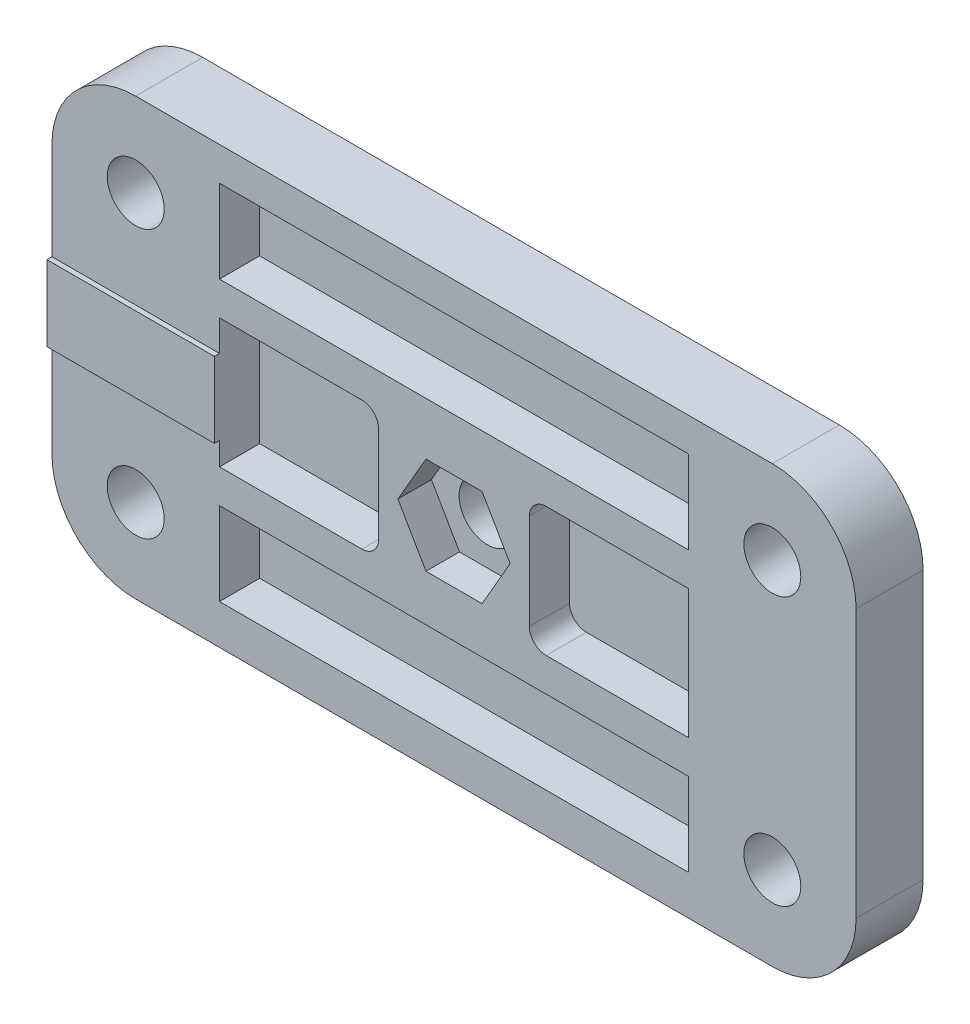
SolidWorks part; units mm, degrees
ref_plane "Front Plane" through (0, 0, 0) normal (0, 0, 1) x (1, 0, 0)
ref_plane "Top Plane" through (0, 0, 0) normal (0, 1, 0) x (1, 0, 0)
ref_plane "Right Plane" through (0, 0, 0) normal (1, 0, 0) x (0, 0, -1)
sketch "Sketch1" plane through (0, 0, 0) normal (0, 0, 1) x (1, 0, 0)
  line L0 (-19, 0) -> (19, 0) construction
  line L1 (-19, -8) -> (19, -8) construction
  line L2 (-19, -8) -> (-19, 8) construction
  line L3 (-19, 8) -> (19, 8) construction
  line L4 (19, -8) -> (19, 8) construction
  line L6 (-19, -13) -> (19, -13)
  line L7 (-24, -8) -> (-24, 8)
  line L8 (-19, 13) -> (19, 13)
  line L9 (24, -8) -> (24, 8)
  circle A0 centre (0, 0) radius 1.7
  circle A1 centre (19, 8) radius 1.7
  circle A2 centre (19, -8) radius 1.7
  circle A3 centre (-19, -8) radius 1.7
  circle A4 centre (-19, 8) radius 1.7
  arc A5 (24, -8) -> (19, -13) centre (19, -8) cw
  arc A6 (-19, -13) -> (-24, -8) centre (-19, -8) cw
  arc A7 (-24, 8) -> (-19, 13) centre (-19, 8) cw
  arc A8 (19, 13) -> (24, 8) centre (19, 8) cw
  dimension "D1" = 3.4
  dimension "D4" = 5
  dimension "D2" = 38
  dimension "D3" = 16
extrude "Boss-Extrude1" add sketch "Sketch1" along normal blind 4
sketch "Sketch2" plane through (0, 0, 4) normal (0, 0, 1) x (1, 0, 0)
  line L1 (3.3486, 0) -> (1.6743, 2.9)
  line L2 (1.6743, 2.9) -> (-1.6743, 2.9)
  line L3 (-1.6743, 2.9) -> (-3.3486, 0)
  line L4 (-3.3486, 0) -> (-1.6743, -2.9)
  line L5 (-1.6743, -2.9) -> (1.6743, -2.9)
  line L6 (1.6743, -2.9) -> (3.3486, 0)
  circle A0 centre (0, 0) radius 2.9 construction
  circle A1 centre (0, 0) radius 1.7 construction
  dimension "D1" = 5.8
extrude "Cut-Extrude1" cut sketch "Sketch2" against normal blind 2
sketch "Sketch3" plane through (0, 0, 4) normal (0, 0, 1) x (1, 0, 0)
  line L0 (24, -8) -> (24, 8) construction
  line L1 (-14, 6.0393) -> (14, 6.0393)
  line L2 (-14, 6.0393) -> (-14, 11)
  line L3 (-14, 11) -> (14, 11)
  line L4 (14, 6.0393) -> (14, 11)
  line L5 (-24, 8) -> (-24, -8) construction
  line L6 (19, 13) -> (-19, 13) construction
  line L7 (-14, 4.0393) -> (-4.5, 4.0393)
  line L8 (-14, 4.0393) -> (-14, -3.6667)
  line L9 (-14, -3.6667) -> (-4.5, -3.6667)
  line L10 (-4.5, 4.0393) -> (-4.5, -3.6667)
  line L11 (4.5, 4.0393) -> (14, 4.0393)
  line L12 (4.5, 4.0393) -> (4.5, -3.6667)
  line L13 (4.5, -3.6667) -> (14, -3.6667)
  line L14 (14, 4.0393) -> (14, -3.6667)
  line L15 (-14, -5.6667) -> (14, -5.6667)
  line L16 (-14, -5.6667) -> (-14, -10.6274)
  line L17 (-14, -10.6274) -> (14, -10.6274)
  line L18 (14, -5.6667) -> (14, -10.6274)
  line L19 (-14, 6.0393) -> (-14, 4.0393) construction
  line L20 (-14, -3.6667) -> (-14, -5.6667) construction
  line L21 (-14, 11) -> (-14, 13) construction
  dimension "D1" = 10
  dimension "D2" = 10
  dimension "D3" = 2
  dimension "D4" = 9
extrude "Cut-Extrude2" cut sketch "Sketch3" against normal blind 2.4
fillet "Fillet1" radius 1 4 edges at (4.5, -3.6667, 2.8) (4.5, 4.0393, 2.8) (-4.5, -3.6667, 2.8) (-4.5, 4.0393, 2.8)
sketch "Sketch4" plane through (0, 0, 4) normal (0, 0, 1) x (1, 0, 0)
  line L0 (-24, 8) -> (-24, -8) construction
  line L1 (-24, -2.3038) -> (-14, -2.3038)
  line L2 (-24, -2.3038) -> (-24, 2.1962)
  line L3 (-24, 2.1962) -> (-14, 2.1962)
  line L4 (-14, -2.3038) -> (-14, 2.1962)
  line L5 (-14, 4.0393) -> (-14, -3.6667) construction
  line L6 (-24, -0.0538) -> (0, 0) construction
  dimension "D1" = 4.5
extrude "Boss-Extrude2" add sketch "Sketch4" along normal blind 0.3
